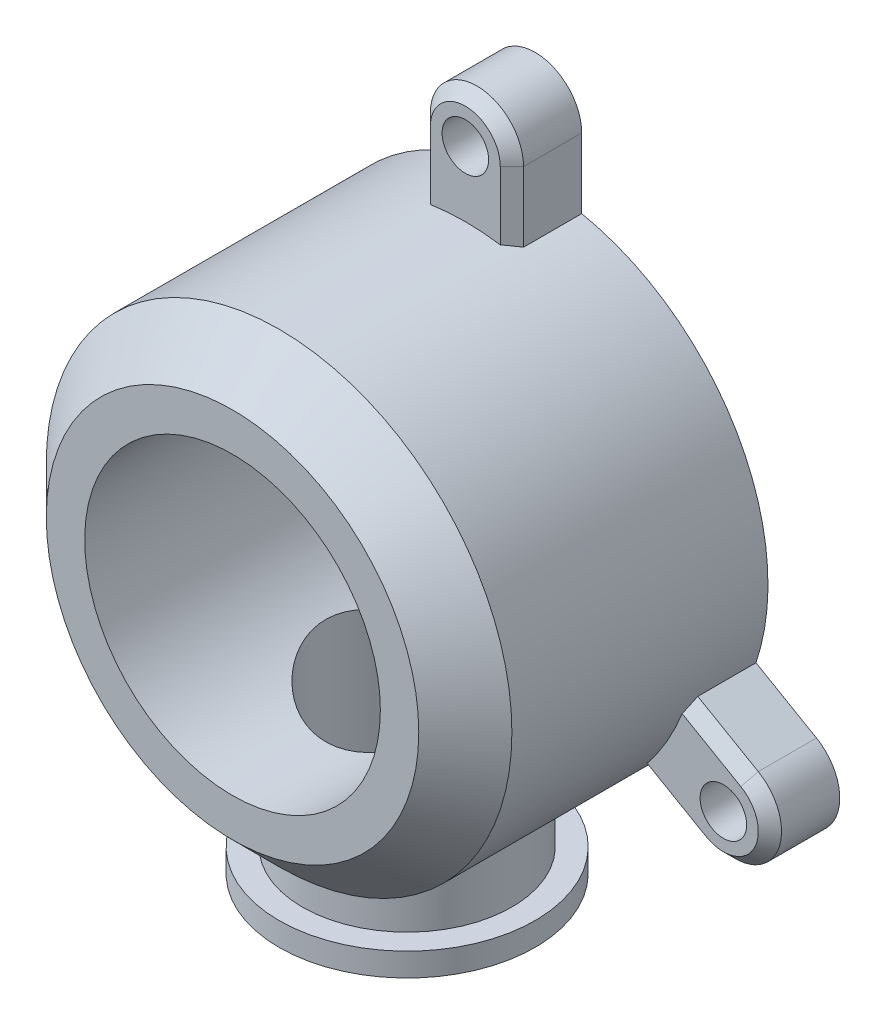
SolidWorks part; units mm, degrees
material "Plain Carbon Steel"
ref_plane "Front Plane" through (0, 0, 0) normal (0, 0, 1) x (1, 0, 0)
ref_plane "Top Plane" through (0, 0, 0) normal (0, 1, 0) x (1, 0, 0)
ref_plane "Right Plane" through (0, 0, 0) normal (1, 0, 0) x (0, 0, -1)
sketch "Sketch1" plane through (0, 0, 0) normal (0, 0, 1) x (1, 0, 0)
  line L0 (0, 0) -> (0, 50) construction
  line L1 (-5, 31.3538) -> (-5, 20.6038)
  line L2 (-5, 20.6038) -> (5, 20.6038)
  line L3 (5, 20.6038) -> (5, 31.3538)
  line L4 (-10, 48.9898) -> (-10, 63.9898)
  line L5 (10, 63.9898) -> (10, 48.9898)
  circle A0 centre (0, 0) radius 31.75
  circle A1 centre (0, 0) radius 50
  arc A2 (-10, 63.9898) -> (10, 63.9898) centre (0, 63.9898) cw
  dimension "D1" = 100
  dimension "D2" = 18.25
  dimension "D3" = 10.75
  dimension "D4" = 10
  dimension "D5" = 20
  dimension "D6" = 15
extrude "Boss-Extrude1" add sketch "Sketch1" along normal blind 65 contours A0 A1 region at (0, 48.5858, 0)
extrude "Boss-Extrude2" add sketch "Sketch1<3>" along normal blind 25 contours L2 L0 A0 L1 | L0 L2 L3 A0 region at (-2.485, 26.1117, 0) region at (2.485, 26.1117, 0)
sketch "Sketch1<3>" plane through (0, 0, 0) normal (0, 0, 1) x (1, 0, 0) same geometry as "Sketch1"
extrude "Boss-Extrude3" add sketch "Sketch1<4>" along normal blind 15 contours A2 L4 A1 L5 region at (0, 60.8645, 0)
sketch "Sketch1<4>" plane through (0, 0, 0) normal (0, 0, 1) x (1, 0, 0) same geometry as "Sketch1"
chamfer "Chamfer2" distance 2.5 angle 45 3 edges at (-10, 56.4898, 15) (0, 73.9898, 15) (10, 56.4898, 15)
hole_wizard "Ø10.0mm Dowel Hole1" positions "Sketch6" profile "Sketch5" hole size "Ø10.0" standard "ANSI Metric" end condition through all
sketch "Sketch6" plane through (0, 0, 15) normal (0, 0, 1) x (1, 0, 0)
  point P0 (0, 63.9898)
sketch "Sketch5" plane through (0, 63.9898, 15) normal (1, 0, 0) x (0, -1, 0)
  line L0 (0, 0) -> (0, 15)
  line L1 (0, 15) -> (5, 15)
  line L2 (5, 15) -> (5, 0)
  line L5 (5, 0) -> (0, 0)
  line L11 (0, -6.35) -> (0, 107.95) construction
  dimension "Thru Hole Dia." = 10
  dimension "Thru Hole Depth" = 15
pattern_circular "CirPattern2" count 3 over 360 about axis through (0, 0, 65) along (0, 0, -1) of "Boss-Extrude3", "Chamfer2", "Ø10.0mm Dowel Hole1"
chamfer "Chamfer1" distance 10 angle 45 1 edges at (50, 0, 65)
ref_plane "Plane1" through (0, -65, 0) normal (0, 1, 0) x (1, 0, 0)
sketch "Sketch2" plane through (0, -65, 0) normal (0, 1, 0) x (1, 0, 0)
  line L0 (50, -55) -> (-50, -55) construction
  line L1 (0, -27.5) -> (0, 0) construction
  circle A0 centre (0, -27.5) radius 27.5
extrude "Boss-Extrude4" add sketch "Sketch2" along normal blind 5 separate body
sketch "Sketch3" plane through (0, -60, 0) normal (0, 1, 0) x (1, 0, 0)
  circle A0 centre (0, -27.5) radius 22.5
  circle A1 centre (0, -27.5) radius 27.5 construction
  dimension "D1" = 5
extrude "Boss-Extrude5" add sketch "Sketch3" along normal up to next
sketch "Sketch4" plane through (0, -65, 0) normal (0, -1, 0) x (1, 0, 0)
  circle A0 centre (0, 27.5) radius 17.5
  circle A1 centre (0, 27.5) radius 27.5 construction
  dimension "D1" = 10
extrude "Cut-Extrude1" cut sketch "Sketch4" against normal up to surface (33.25 mm away) up to face at (31.75, 0, 65)
